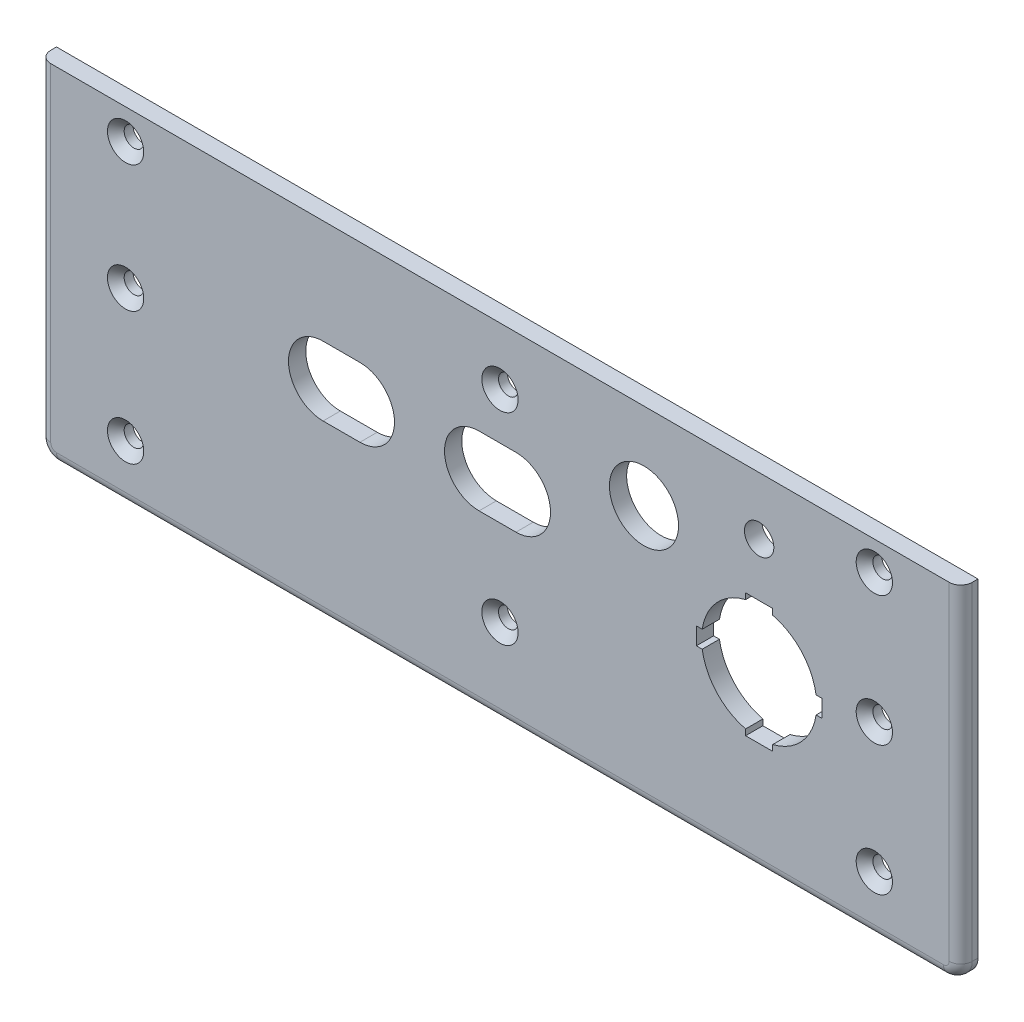
SolidWorks part; units mm, degrees
ref_plane "Front Plane" through (0, 0, 0) normal (0, 0, 1) x (1, 0, 0)
ref_plane "Top Plane" through (0, 0, 0) normal (0, 1, 0) x (1, 0, 0)
ref_plane "Right Plane" through (0, 0, 0) normal (1, 0, 0) x (0, 0, -1)
sketch "Sketch11" plane through (0, 0, 0) normal (0, 0, 1) x (1, 0, 0)
  line L0 (-44.8869, 31.5) -> (-45.8972, 31.5)
  line L1 (-45.8972, 31.5) -> (-45.8972, 28.5)
  line L2 (-45.8972, 28.5) -> (-44.8869, 28.5)
  line L3 (-35, 30) -> (-45.8972, 30) construction
  line L4 (-37.35, 20.28) -> (-37.35, 19.254)
  line L5 (-37.35, 19.254) -> (-32.65, 19.254)
  line L6 (-32.65, 19.254) -> (-32.65, 20.28)
  line L7 (-35, 30) -> (-35, 19.254) construction
  line L8 (-32.65, 40.746) -> (-32.65, 39.72)
  line L9 (-37.35, 40.746) -> (-32.65, 40.746)
  line L10 (-37.35, 39.72) -> (-37.35, 40.746)
  line L11 (-35, 18.7315) -> (-35, 30) construction
  line L12 (-25.1131, 31.5) -> (-24.1028, 31.5)
  line L13 (-24.1028, 31.5) -> (-24.1028, 28.5)
  line L14 (-24.1028, 28.5) -> (-25.1131, 28.5)
  line L15 (-35, 50) -> (-35, 30) construction
  line L17 (0, 0) -> (-160, 0)
  line L18 (0, 0) -> (0, 60)
  line L19 (0, 60) -> (-160, 60)
  line L20 (-160, 0) -> (-160, 60)
  line L21 (-83.6273, 35.9303) -> (-77.2273, 35.9303) construction
  line L22 (-83.6273, 41.9303) -> (-77.2273, 41.9303)
  line L23 (-83.6273, 29.9303) -> (-77.2273, 29.9303)
  line L24 (-110.7157, 35.9) -> (-104.3157, 35.9) construction
  line L25 (-110.7157, 41.9) -> (-104.3157, 41.9)
  line L26 (-110.7157, 29.9) -> (-104.3157, 29.9)
  arc A0 (-44.8869, 28.5) -> (-37.35, 20.28) centre (-35, 30) ccw
  circle A1 centre (-35, 30) radius 11 construction
  arc A2 (-32.65, 20.28) -> (-25.1131, 28.5) centre (-35, 30) ccw
  arc A3 (-37.35, 39.72) -> (-44.8869, 31.5) centre (-35, 30) ccw
  arc A4 (-25.1131, 31.5) -> (-32.65, 39.72) centre (-35, 30) ccw
  circle A5 centre (-35, 50) radius 2.55
  circle A6 centre (-55, 45) radius 6
  arc A7 (-103.7657, 35.9) -> (-104.3157, 36.45) centre (-104.3157, 35.9) ccw construction
  arc A8 (-110.7157, 36.45) -> (-111.2657, 35.9) centre (-110.7157, 35.9) ccw construction
  arc A9 (-76.6773, 35.9303) -> (-77.2273, 36.4803) centre (-77.2273, 35.9303) ccw construction
  arc A10 (-83.6273, 36.4803) -> (-84.1773, 35.9303) centre (-83.6273, 35.9303) ccw construction
  arc A11 (-103.7657, 35.9) -> (-104.3157, 36.45) centre (-104.3157, 35.9) ccw construction
  arc A12 (-110.7157, 36.45) -> (-111.2657, 35.9) centre (-110.7157, 35.9) ccw construction
  arc A13 (-76.6773, 35.9303) -> (-77.2273, 36.4803) centre (-77.2273, 35.9303) ccw construction
  arc A14 (-83.6273, 36.4803) -> (-84.1773, 35.9303) centre (-83.6273, 35.9303) ccw construction
  arc A15 (-83.6273, 41.9303) -> (-83.6273, 29.9303) centre (-83.6273, 35.9303) ccw
  arc A16 (-77.2273, 29.9303) -> (-77.2273, 41.9303) centre (-77.2273, 35.9303) ccw
  arc A17 (-110.7157, 41.9) -> (-110.7157, 29.9) centre (-110.7157, 35.9) ccw
  arc A18 (-104.3157, 29.9) -> (-104.3157, 41.9) centre (-104.3157, 35.9) ccw
  point P42 (-80.4273, 35.9303)
  point P47 (-107.5157, 35.9)
  point P52 (-104.3157, 43.9303)
  dimension "D1" = 20
  dimension "D4" = 22
  dimension "D5" = 5.1
  dimension "D11" = 12
  dimension "D6" = 20
  dimension "D2" = 3
  dimension "D3" = 4.7
  dimension "D7" = 160
  dimension "D8" = 35
  dimension "D9" = 30
  dimension "D10" = 60
  dimension "D12" = 20
  dimension "D13" = 12
  dimension "D14" = 15
extrude "Boss-Extrude1" add sketch "Sketch11" along normal blind 3 contours L20 L17 L18 L19 A5 A4 L12 L13 L14 A2 L6 L5 L4 A0 L2 L1 L0 A3 L10 L9 L8 region at (-81.5053, 29.5032, 0)
fillet "Fillet1" radius 2 3 edges at (-80, 0, 3) (-160, 30, 3) (0, 30, 3)
fillet "Fillet3" radius 3 4 edges at (-0.5858, 0.5858, 2.4142) (-159.4142, 0.5858, 2.4142) (-160, 0, 0.5) (0, 0, 0.5)
sketch "Sketch12" plane through (0, 0, 3) normal (0, 0, 1) x (1, 0, 0)
  line L1 (-80, 50) -> (-80, 60) construction
  line L2 (-2, 60) -> (-158, 60) construction
  circle A0 centre (-145, 9.7613) radius 3 construction
  circle A1 centre (-145, 32.7387) radius 3 construction
  circle A2 centre (-145, 54.7613) radius 3 construction
  circle A3 centre (-15, 10) radius 3 construction
  circle A4 centre (-15, 32.5) radius 3 construction
  circle A5 centre (-15, 55) radius 3 construction
  circle A6 centre (-145, 9.7613) radius 3
  circle A7 centre (-145, 32.7387) radius 3
  circle A8 centre (-145, 54.7613) radius 3
  circle A9 centre (-15, 10) radius 3
  circle A10 centre (-15, 32.5) radius 3
  circle A11 centre (-15, 55) radius 3
  circle A12 centre (-80, 50) radius 3
  circle A13 centre (-80, 15) radius 3
  circle A14 centre (-80, 50) radius 3 construction
  circle A15 centre (-80, 15) radius 3 construction
hole_wizard "CSK for M3 Flat Head Machine Screw1" positions "3DSketch1" profile "Sketch13" countersink size "M3" standard "ANSI Metric" end condition through all
sketch3d "3DSketch1"
  point P0 (-145, 54.7613, 3)
  point P3 (-145, 32.7387, 3)
  point P6 (-145, 9.7613, 3)
  point P9 (-15, 10, 3)
  point P12 (-15, 32.5, 3)
  point P15 (-15, 55, 3)
  point P18 (-80, 50, 3)
  point P21 (-80, 15, 3)
sketch "Sketch13" plane through (-145, 54.7613, 3) normal (1, 0, 0) x (0, -1, 0)
  line L0 (0, 0) -> (0, 3)
  line L1 (0, 3) -> (1.7, 3)
  line L2 (1.7, 3) -> (1.7, 1.45)
  line L3 (1.7, 1.45) -> (3.15, 0)
  line L5 (3.15, 0) -> (0, 0)
  line L6 (-1.7, 1.45) -> (-3.15, 0) construction
  line L11 (0, -6.35) -> (0, 107.95) construction
  dimension "Thru Hole Dia." = 3.4
  dimension "Thru Hole Depth" = 3
  dimension "Near C'Sink Dia." = 6.3
  dimension "Near C'Sink Angle" = 90
